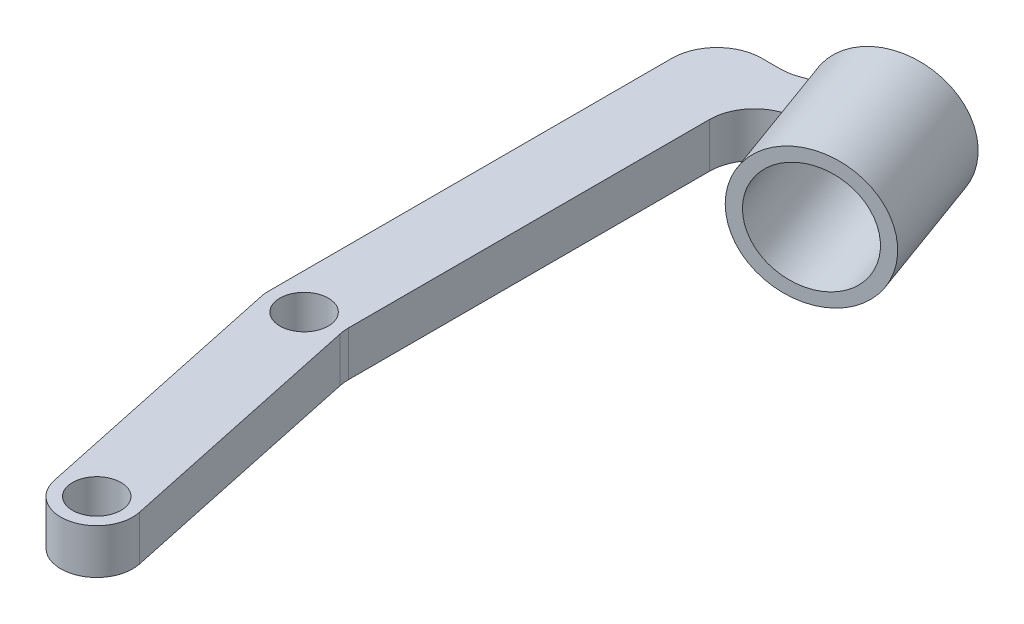
SolidWorks part; units mm, degrees
ref_plane "Front Plane" through (0, 0, 0) normal (0, 0, 1) x (1, 0, 0)
ref_plane "Top Plane" through (0, 0, 0) normal (0, 1, 0) x (1, 0, 0)
ref_plane "Right Plane" through (0, 0, 0) normal (1, 0, 0) x (0, 0, -1)
sketch "Sketch1" plane through (0, 0, 0) normal (0, 1, 0) x (1, 0, 0)
  line L0 (-1000, 0) -> (49000, 0) construction
  line L1 (-10.1499, 28.5128) -> (-3.9126, -0.8316)
  line L2 (3.9126, 0.8316) -> (-2.2374, 29.7648)
  line L3 (-10.2374, 29.3444) -> (-10.2374, 79.3444)
  line L5 (-6.2374, 29.3444) -> (0, 0) construction
  line L6 (-10.2374, 79.3444) -> (-2.2374, 79.3444)
  line L7 (-2.2374, 29.7648) -> (-2.2374, 74.0235)
  line L8 (-2.2374, 74.0235) -> (13.5681, 79.7763)
  line L9 (13.5681, 79.7763) -> (11.858, 84.4747)
  line L10 (11.858, 84.4747) -> (-2.2374, 79.3444)
  arc A0 (-3.9126, -0.8316) -> (3.9126, 0.8316) centre (0, 0) ccw
  arc A3 (-10.2374, 29.3444) -> (-10.1499, 28.5128) centre (-6.2374, 29.3444) ccw
  circle A4 centre (-6.2374, 29.3444) radius 2.7
  circle A5 centre (0, 0) radius 2.7
  circle A7 centre (-6.2374, 29.3444) radius 4 construction
  dimension "D1" = 8
  dimension "D2" = 5.4
  dimension "D7" = 5.4
  dimension "D6" = 8
  dimension "D4" = 78
  dimension "D5" = 30
  dimension "D3" = 50
  dimension "D8" = 20
  dimension "D9" = 5
  dimension "D10" = 15
extrude "Boss-Extrude2" add sketch "Sketch1" along normal blind 5
fillet "Fillet2" radius 5 4 edges at (-2.2374, 2.5, -79.3444) (-10.2374, 2.5, -79.3444) (-2.2374, 2.5, -74.0235) (-2.2374, 2.5, -29.7648)
sketch "Sketch2" plane through (-25.7625, 0, -70.782) normal (-0.342, 0, -0.9397) x (-0.9397, 0, 0.342)
  circle A0 centre (-34.01, 2.5) radius 7.5
  circle A1 centre (-34.01, 2.5) radius 6
  line M1 (-40.035, 0) -> (-25.9166, 0)
  line M3 (-25.9166, 5) -> (-40.035, 5)
  dimension "D1" = 15
  dimension "D2" = 12
extrude "Boss-Extrude3" add sketch "Sketch2" against normal blind 15
extrude "Cut-Extrude1" cut sketch "Sketch2<2>" against normal blind 15 contours A1 M3 M1 region at (6.1965, 2.5, -82.4141)
sketch "Sketch2<2>" plane through (-25.7625, 0, -70.782) normal (-0.342, 0, -0.9397) x (-0.9397, 0, 0.342) same geometry as "Sketch2"
equation "\"D7@Sketch1\"=\"D2@Sketch1\""
